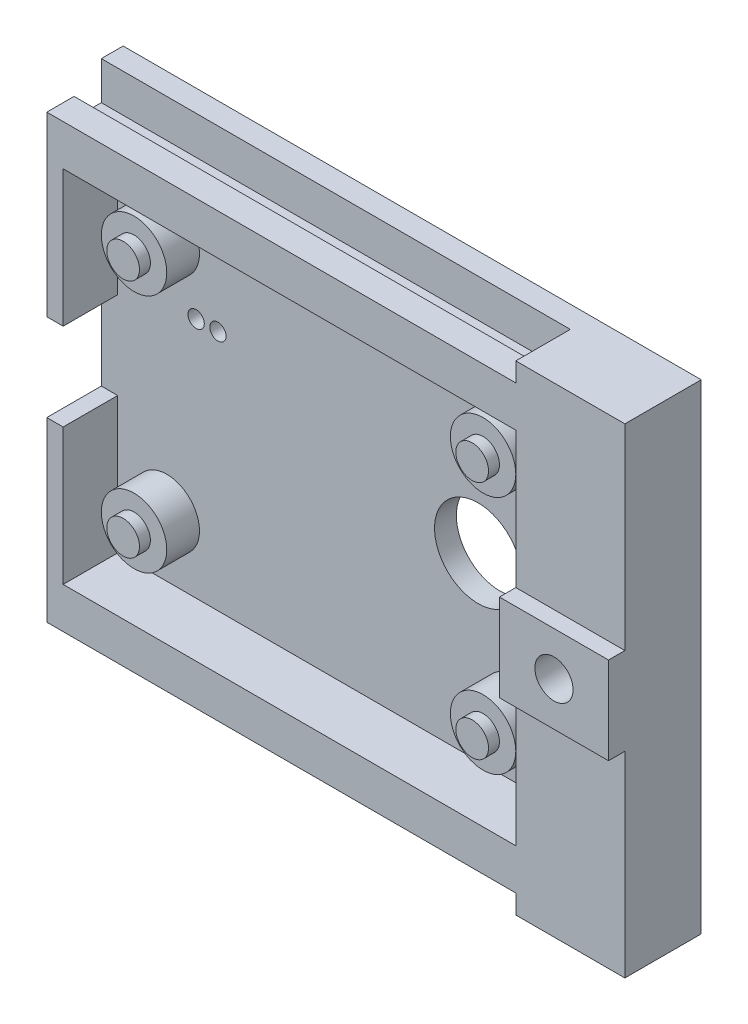
SolidWorks part; units mm, degrees
ref_plane "Alzado" through (0, 0, 0) normal (0, 0, 1) x (1, 0, 0)
ref_plane "Planta" through (0, 0, 0) normal (0, 1, 0) x (1, 0, 0)
ref_plane "Vista lateral" through (0, 0, 0) normal (1, 0, 0) x (0, 0, -1)
sketch "Croquis1" plane through (0, 0, 0) normal (0, 0, 1) x (1, 0, 0)
  line L0 (-22, 22) -> (-22, -22)
  line L1 (-22, -22) -> (31, -22)
  line L2 (31, -22) -> (31, 22)
  line L3 (31, 22) -> (-22, 22)
  line L13 (-20, 15) -> (20, 15) construction
  line L14 (-20, 15) -> (-20, -15) construction
  line L15 (-20, -15) -> (20, -15) construction
  line L16 (20, 15) -> (20, -15) construction
  line L17 (-20, 15) -> (20, -15) construction
  line L18 (-20, -15) -> (20, 15) construction
  circle A0 centre (-13.3084, 5.6686) radius 0.75
  circle A1 centre (-11.3084, 5.6686) radius 0.75
  circle A2 centre (12.55, 0) radius 4
  point P0 (0, 0)
  point P3 (-22, 0)
  point P6 (12.55, 0)
  point P8 (0, 0)
  dimension "D9" = 2
  dimension "D10" = 1.5
  dimension "D3" = 8
  dimension "D1" = 44
  dimension "D2" = 2
  dimension "D5" = 7.45
  dimension "D6" = 40
  dimension "D7" = 30
  dimension "D8" = 11
  dimension "D11" = 6.6916
  dimension "D12" = 20.6686
extrude "Saliente-Extruir1" add sketch "Croquis1" along normal blind 2
sketch "Croquis4" plane through (0, 0, 2) normal (0, 0, 1) x (1, 0, 0)
  line L1 (-20, 15) -> (20, 15) construction
  line L2 (-20, 15) -> (-20, -15) construction
  line L3 (-20, -15) -> (20, -15) construction
  line L4 (20, 15) -> (20, -15) construction
  line L5 (-20, 15) -> (20, -15) construction
  line L6 (-20, -15) -> (20, 15) construction
  circle A0 centre (-16, -11) radius 1.5
  circle A1 centre (16, -11) radius 1.5
  circle A2 centre (16, 11) radius 1.5
  circle A3 centre (-16, 11) radius 1.5
  point P12 (0, 0)
  dimension "D1" = 3
  dimension "D2" = 30
  dimension "D3" = 40
  dimension "D4" = 4
  dimension "D5" = 4
  dimension "D6" = 4
  dimension "D7" = 4
extrude "Saliente-Extruir3" add sketch "Croquis4" along normal blind 4
sketch "Croquis5" plane through (0, 0, 0) normal (0, 0, -1) x (-1, 0, 0)
  line L0 (-31, -22) -> (-31, 22) construction
  circle A0 centre (-26, 0) radius 1.75
  dimension "D2" = 3.5
  dimension "D1" = 5
extrude "Cortar-Extruir1" cut sketch "Croquis5" against normal up to next
sketch "Croquis6" plane through (0, 0, 2) normal (0, 0, 1) x (1, 0, 0)
  line L0 (-22, -18.5) -> (21, -18.5)
  line L1 (-22, 22) -> (-22, -22) construction
  line L3 (-22, -18.5) -> (-22, 18.5)
  line L4 (-20.5, -16.5) -> (21, -16.5)
  line L7 (-20.5, 16.5) -> (21, 16.5)
  line L8 (-20.5, -16.5) -> (-20.5, 16.5)
  line L9 (21, 18.5) -> (-22, 18.5)
  line L11 (21, -18.5) -> (21, -22)
  line L12 (-22, -22) -> (31, -22) construction
  line L13 (21, -22) -> (31, -22)
  line L14 (31, -22) -> (31, 22)
  line L15 (31, 22) -> (21, 22)
  line L16 (31, 22) -> (-22, 22) construction
  line L17 (21, 22) -> (21, 18.5)
  line L18 (21, -16.5) -> (21, 16.5)
  circle A0 centre (26, 0) radius 1.75 construction
  circle A1 centre (26, 0) radius 1.75
  dimension "D1" = 37
  dimension "D2" = 2
  dimension "D3" = 2
  dimension "D4" = 18.5
  dimension "D5" = 43
  dimension "D6" = 1.5
extrude "Saliente-Extruir4" add sketch "Croquis6" along normal blind 5
sketch "Croquis7" plane through (0, 0, 7) normal (0, 0, 1) x (1, 0, 0)
  line L0 (-22, 18.5) -> (-22, 20.25)
  line L1 (-22, 22) -> (-22, 18.5) construction
  line L2 (-22, 20.25) -> (21, 20.25)
  line L3 (21, 22) -> (21, 18.5) construction
  line L4 (21, 20.25) -> (21, 18.5)
  line L5 (21, 18.5) -> (-22, 18.5)
  line L6 (-22, -18.5) -> (-22, -20.25)
  line L7 (-22, -18.5) -> (-22, -22) construction
  line L8 (-22, -20.25) -> (21, -20.25)
  line L9 (21, -18.5) -> (21, -22) construction
  line L10 (21, -20.25) -> (21, -18.5)
  line L11 (21, -18.5) -> (-22, -18.5)
extrude "Saliente-Extruir5" add sketch "Croquis7" against normal blind 2.5
sketch "Croquis8" plane through (0, 0, 7) normal (0, 0, 1) x (1, 0, 0)
  line L0 (-20.5, -4) -> (-20.5, 4)
  line L1 (-20.5, 16.5) -> (-20.5, -16.5) construction
  line L2 (-20.5, 4) -> (-22, 4)
  line L3 (-22, 20.25) -> (-22, -20.25) construction
  line L4 (-22, 4) -> (-22, -4)
  line L5 (-22, -4) -> (-20.5, -4)
  point P4 (-20.5, 0)
  dimension "D1" = 8
extrude "Cortar-Extruir3" cut sketch "Croquis8" against normal blind 5
sketch "Croquis9" plane through (0, 0, 0) normal (0, 0, -1) x (-1, 0, 0)
  circle A0 centre (-26, 0) radius 3.5
  dimension "D1" = 7
extrude "Cortar-Extruir4" cut sketch "Croquis9" against normal blind 5
sketch "Croquis10" plane through (0, 0, 2) normal (0, 0, 1) x (1, 0, 0)
  circle A0 centre (-16, 11) radius 3
  circle A1 centre (16, 11) radius 3
  circle A2 centre (16, -11) radius 3
  circle A3 centre (-16, -11) radius 3
  dimension "D1" = 6
extrude "Saliente-Extruir6" add sketch "Croquis10" along normal blind 3
sketch "Croquis12" plane through (0, 0, 7) normal (0, 0, 1) x (1, 0, 0)
  line L0 (21, -4) -> (21, 4)
  line L1 (21, -16.5) -> (21, 16.5) construction
  line L2 (21, -4) -> (31, -4)
  line L3 (31, -22) -> (31, 22) construction
  line L4 (31, -4) -> (31, 4)
  line L5 (31, 4) -> (21, 4)
  circle A0 centre (26, 0) radius 1.75 construction
  circle A1 centre (26, 0) radius 1.75
  point P4 (21, 0)
  dimension "D1" = 8
extrude "Saliente-Extruir7" add sketch "Croquis12" along normal blind 1.5
